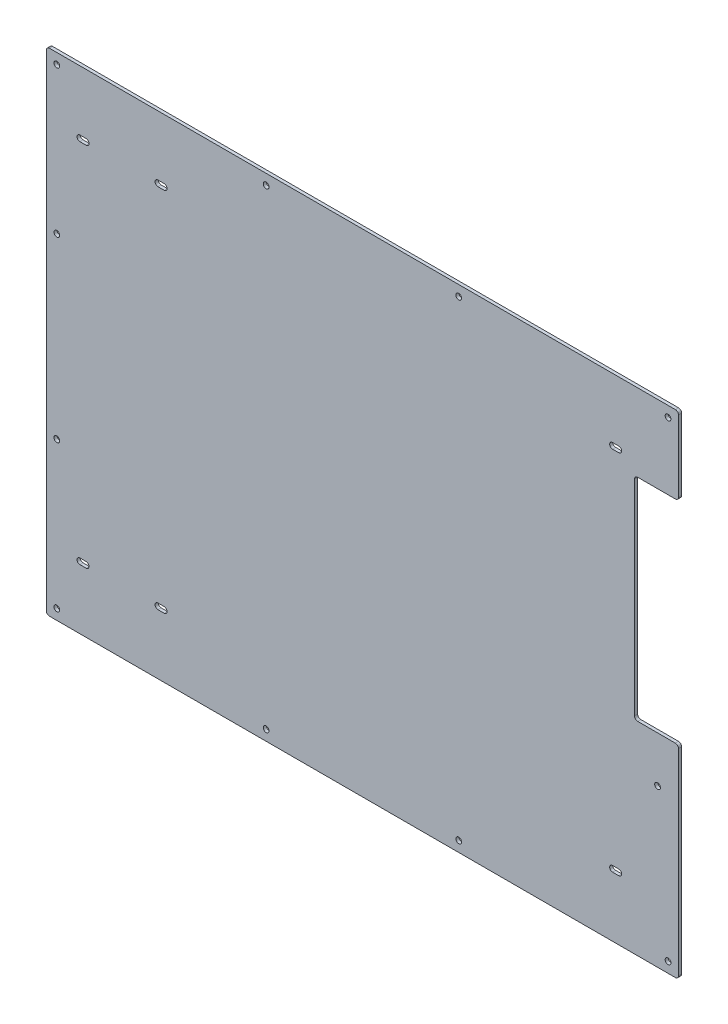
SolidWorks part; units mm, degrees
material "Acrylic (Medium-high impact)"
ref_plane "Front" through (0, 0, 0) normal (0, 0, 1) x (1, 0, 0)
ref_plane "Top" through (0, 0, 0) normal (0, 1, 0) x (1, 0, 0)
ref_plane "Right" through (0, 0, 0) normal (1, 0, 0) x (0, 0, -1)
sketch "Sketch1" plane through (0, 0, 0) normal (0, 0, 1) x (1, 0, 0)
  line L0 (0, 450) -> (604, 450) construction
  line L1 (0, 0) -> (604, 0)
  line L2 (0, 0) -> (0, 470)
  line L3 (0, 470) -> (604, 470)
  line L4 (604, 0) -> (604, 470)
  dimension "D1" = 604
  dimension "D2" = 470
  dimension "D3" = 20
extrude "Boss-Extrude1" add sketch "Sketch1" along normal blind 3
fillet "Fillet1" radius 3 4 edges at (0, 0, 1.5) (604, 0, 1.5) (0, 470, 1.5) (604, 470, 1.5)
hole_wizard "M5 Clearance Hole1" positions "Sketch4" profile "Sketch3" hole size "M5" standard "ANSI Metric" end condition through all
sketch "Sketch4" plane through (0, 0, 0) normal (0, 0, -1) x (-1, 0, 0)
  line L0 (-210, 460) -> (-10, 460) construction
  line L1 (-10, 460) -> (0, 460) construction
  line L2 (0, 467) -> (0, 3) construction
  line L5 (-210, 460) -> (-246, 460) construction
  line L8 (-302, 470) -> (-302, 460) construction
  line L9 (-601, 470) -> (-3, 470) construction
  line L10 (-358, 460) -> (-246, 460) construction
  line L14 (-394, 460) -> (-358, 460) construction
  line L15 (-594, 460) -> (-604, 460) construction
  line L16 (-394, 460) -> (-594, 460) construction
  line L17 (-10, 10) -> (0, 10) construction
  line L20 (-10, 10) -> (-210, 10) construction
  line L21 (-210, 10) -> (-246, 10) construction
  line L22 (-246, 10) -> (-358, 10) construction
  line L27 (-210, 460) -> (-210, 10) construction
  line L30 (-10, 10) -> (-10, 460) construction
  line L32 (-394, 10) -> (-358, 10) construction
  line L33 (-594, 10) -> (-394, 10) construction
  line L34 (-594, 10) -> (-604, 10) construction
  line L35 (-3, 0) -> (-601, 0) construction
  line L36 (-544, 470) -> (-544, 410) construction
  line L37 (-601, 470) -> (-3, 470) construction
  line L38 (-544, 410) -> (-544, 60) construction
  line L39 (-544, 60) -> (-544, 0) construction
  line L40 (-3, 0) -> (-601, 0) construction
  line L43 (-604, 3) -> (-604, 467) construction
  line L44 (-35, 470) -> (-35, 410) construction
  line L45 (-35, 410) -> (-35, 60) construction
  line L46 (-35, 60) -> (-35, 0) construction
  line L49 (0, 467) -> (0, 3) construction
  line L50 (-109.625, 470) -> (-109.625, 410) construction
  line L51 (-109.625, 410) -> (-109.625, 60) construction
  line L52 (-109.625, 60) -> (-109.625, 0) construction
  point P0 (-594, 460)
  point P2 (-394, 460)
  point P4 (-210, 460)
  point P6 (-10, 460)
  point P8 (-10, 10)
  point P10 (-210, 10)
  point P12 (-394, 10)
  point P14 (-594, 10)
  point P98 (-544, 410)
  point P102 (-544, 60)
  point P120 (-35, 410)
  point P122 (-35, 60)
  point P138 (-109.625, 410)
  point P140 (-109.625, 60)
  dimension "D1" = 10
  dimension "D2" = 200
  dimension "D4" = 10
  dimension "D5" = 10
  dimension "D6" = 60
  dimension "D7" = 60
  dimension "D8" = 35
  dimension "D9" = 109.625
sketch "Sketch3" plane through (594, 460, 0) normal (1, 0, 0) x (0, 1, 0)
  line L0 (0, 0) -> (0, 3)
  line L1 (0, 3) -> (2.75, 3)
  line L2 (2.75, 3) -> (2.75, 0)
  line L5 (2.75, 0) -> (0, 0)
  line L11 (0, -6.35) -> (0, 107.95) construction
  dimension "Thru Hole Dia." = 5.5
  dimension "Thru Hole Depth" = 3
hole_wizard "M5 Manufacturing Fixturing Hole" positions "Sketch12" profile "Sketch13" hole size "M5" standard "ANSI Metric" end condition through all
sketch "Sketch12" plane through (0, 0, 3) normal (0, 0, 1) x (1, 0, 0)
  line L0 (0, 467) -> (0, 3) construction
  line L1 (10, 320) -> (10, 150) construction
  line L4 (10, 150) -> (10, 0) construction
  line L5 (3, 0) -> (601, 0) construction
  line L8 (10, 320) -> (10, 470) construction
  line L9 (601, 470) -> (3, 470) construction
  line L11 (584, 470) -> (584, 320) construction
  line L12 (584, 320) -> (584, 150) construction
  line L13 (584, 150) -> (584, 0) construction
  line L16 (604, 3) -> (604, 467) construction
  point P0 (10, 320)
  point P2 (10, 150)
  point P28 (584, 320)
  point P30 (584, 150)
  dimension "D1" = 10
  dimension "D2" = 150
  dimension "D3" = 320
  dimension "D4" = 20
sketch "Sketch13" plane through (10, 320, 3) normal (1, 0, 0) x (0, -1, 0)
  line L0 (0, 0) -> (0, 3)
  line L1 (0, 3) -> (2.75, 3)
  line L2 (2.75, 3) -> (2.75, 0)
  line L5 (2.75, 0) -> (0, 0)
  line L11 (0, -6.35) -> (0, 107.95) construction
  dimension "Thru Hole Dia." = 5.5
  dimension "Thru Hole Depth" = 3
sketch "Sketch5" [suppressed] plane through (0, 0, 3) normal (0, 0, 1) x (1, 0, 0)
  line L0 (3, 0) -> (601, 0) construction
  line L1 (566.25, 20) -> (594.25, 20)
  line L2 (566.25, 20) -> (566.25, 67)
  line L3 (566.25, 67) -> (594.25, 67)
  line L4 (594.25, 20) -> (594.25, 67)
  line L5 (604, 3) -> (604, 467) construction
  line L6 (566.25, 43.5) -> (560.25, 43.5) construction
  line L7 (580.25, 67) -> (580.25, 20) construction
  line L9 (545.25, 14.25) -> (573.25, 14.25) construction
  circle A0 centre (560.25, 43.5) radius 1.6
  circle A1 centre (600.25, 43.5) radius 1.6
  circle A2 centre (394, 10) radius 4.75 construction
  circle A4 centre (594, 10) radius 4.75 construction
  dimension "D5" = 3.2
  dimension "D6" = 40
  dimension "D3" = 3.75
  dimension "D7" = 9.5
  dimension "D1" = 20
  dimension "D2" = 47
  dimension "D4" = 28
  dimension "D8" = 5.75
extrude "PSU Cutout" [suppressed] cut sketch "Sketch5" against normal through all
fillet "Fillet2" [suppressed] radius 0.5
sketch "Sketch9" plane through (0, 0, 3) normal (0, 0, 1) x (1, 0, 0)
  line L0 (32, 410) -> (38, 410) construction
  line L1 (32, 412.75) -> (38, 412.75)
  line L2 (32, 407.25) -> (38, 407.25)
  line L3 (106.625, 410) -> (112.625, 410) construction
  line L4 (106.625, 412.75) -> (112.625, 412.75)
  line L5 (106.625, 407.25) -> (112.625, 407.25)
  line L6 (32, 60) -> (38, 60) construction
  line L7 (32, 62.75) -> (38, 62.75)
  line L8 (32, 57.25) -> (38, 57.25)
  line L9 (106.625, 60) -> (112.625, 60) construction
  line L10 (106.625, 62.75) -> (112.625, 62.75)
  line L11 (106.625, 57.25) -> (112.625, 57.25)
  line L12 (541, 410) -> (547, 410) construction
  line L13 (541, 412.75) -> (547, 412.75)
  line L14 (541, 407.25) -> (547, 407.25)
  line L15 (541, 60) -> (547, 60) construction
  line L16 (541, 62.75) -> (547, 62.75)
  line L17 (541, 57.25) -> (547, 57.25)
  arc A0 (32, 412.75) -> (32, 407.25) centre (32, 410) ccw
  arc A1 (38, 407.25) -> (38, 412.75) centre (38, 410) ccw
  circle A2 centre (35, 410) radius 2.75 construction
  arc A3 (106.625, 412.75) -> (106.625, 407.25) centre (106.625, 410) ccw
  arc A4 (112.625, 407.25) -> (112.625, 412.75) centre (112.625, 410) ccw
  circle A5 centre (109.625, 410) radius 2.75 construction
  arc A6 (32, 62.75) -> (32, 57.25) centre (32, 60) ccw
  arc A7 (38, 57.25) -> (38, 62.75) centre (38, 60) ccw
  arc A8 (106.625, 62.75) -> (106.625, 57.25) centre (106.625, 60) ccw
  arc A9 (112.625, 57.25) -> (112.625, 62.75) centre (112.625, 60) ccw
  arc A10 (541, 412.75) -> (541, 407.25) centre (541, 410) ccw
  arc A11 (547, 407.25) -> (547, 412.75) centre (547, 410) ccw
  arc A12 (541, 62.75) -> (541, 57.25) centre (541, 60) ccw
  arc A13 (547, 57.25) -> (547, 62.75) centre (547, 60) ccw
  circle A14 centre (544, 410) radius 2.75 construction
  circle A15 centre (544, 410) radius 2.75 construction
  circle A16 centre (544, 60) radius 2.75 construction
  circle A17 centre (544, 60) radius 2.75 construction
  circle A18 centre (35, 60) radius 2.75 construction
  circle A19 centre (35, 60) radius 2.75 construction
  circle A20 centre (109.625, 60) radius 2.75 construction
  circle A21 centre (109.625, 60) radius 2.75 construction
  circle A22 centre (35, 410) radius 2.75 construction
  circle A23 centre (109.625, 410) radius 2.75 construction
  point P2 (35, 410)
  point P12 (109.625, 410)
  point P22 (35, 60)
  point P29 (109.625, 60)
  point P37 (544, 410)
  point P45 (544, 60)
  dimension "D1" = 6
extrude "Cut-Extrude5" cut sketch "Sketch9" against normal through all
sketch "Sketch6" plane through (0, 0, 3) normal (0, 0, 1) x (1, 0, 0)
  line L0 (604, 3) -> (604, 467) construction
  line L1 (604, 396) -> (562, 396)
  line L2 (604, 396) -> (604, 194)
  line L3 (604, 194) -> (562, 194)
  line L4 (562, 396) -> (562, 194)
  line L5 (601, 470) -> (3, 470) construction
  dimension "D1" = 42
  dimension "D2" = 202
  dimension "D3" = 276
extrude "Cut-Extrude2" cut sketch "Sketch6" against normal through all
fillet "Fillet3" radius 3 4 edges at (562, 194, 1.5) (562, 396, 1.5) (604, 194, 1.5) (604, 396, 1.5)
sketch "Sketch7" [suppressed] plane through (0, 0, 3) normal (0, 0, 1) x (1, 0, 0)
  line L0 (523, 0) -> (523, 70) construction
  line L1 (3, 0) -> (601, 0) construction
  line L2 (523, 70) -> (604, 70) construction
  line L3 (604, 3) -> (604, 467) construction
  line L4 (513, 0) -> (513, 80)
  line L5 (513, 80) -> (604, 80)
  line L6 (604, 80) -> (604, 470)
  line L7 (604, 470) -> (0, 470)
  line L8 (0, 470) -> (0, 0)
  line L9 (0, 0) -> (513, 0)
  line L10 (601, 470) -> (3, 470) construction
  circle A0 centre (523, 60) radius 2.75 construction
  dimension "D1" = 10
  dimension "D2" = 10
  dimension "D3" = 10
extrude "Cut-Extrude3" [suppressed] cut sketch "Sketch7" against normal through all
fillet "Fillet4" [suppressed] radius 3
sketch "Sketch8" [suppressed] plane through (0, 0, 3) normal (0, 0, 1) x (1, 0, 0)
  line L0 (523, 60) -> (523, 10) construction
  line L1 (523, 10) -> (599, 10) construction
  circle A0 centre (523, 10) radius 2.65
  dimension "D1" = 5.3
extrude "Cut-Extrude4" [suppressed] cut sketch "Sketch8" against normal through all
sketch "Sketch10" [suppressed] plane through (0, 0, 3) normal (0, 0, 1) x (1, 0, 0)
  line L1 (604, 20) -> (554, 20)
  line L2 (604, 20) -> (604, 100)
  line L3 (604, 100) -> (554, 100)
  line L4 (554, 20) -> (554, 100)
  line L5 (604, 3) -> (604, 467) construction
  line L6 (3, 0) -> (601, 0) construction
  dimension "D1" = 80
  dimension "D2" = 50
  dimension "D3" = 20
extrude "Cut-Extrude6" [suppressed] cut sketch "Sketch10" against normal through all
fillet "Fillet5" [suppressed] radius 3
other "120V Side Move Face" [suppressed] offset 0.0762 parameters "D1"=0.0762
other "Ethernet Side Move Face" [suppressed] offset 0.0762 parameters "D1"=0.0762
sketch "Sketch11" [suppressed] plane through (0, 0, 3) normal (0, 0, 1) x (1, 0, 0)
  line L0 (554, 20) -> (555.1225, 21.1225) construction
  line L1 (554, 20) -> (601, 20) construction
  line L2 (554, 100) -> (555.1225, 98.8775) construction
  line L3 (601, 100) -> (554, 100) construction
  circle A0 centre (555.1225, 21.1225) radius 1.5875
  circle A1 centre (555.1225, 98.8775) radius 1.5875
  dimension "D3" = 45
  dimension "D1" = 45
  dimension "D2" = 1.5875
  dimension "D4" = 1.5875
extrude "Cut-Extrude7" [suppressed] cut sketch "Sketch11" against normal through all
fillet "Fillet6" [suppressed] radius 1
